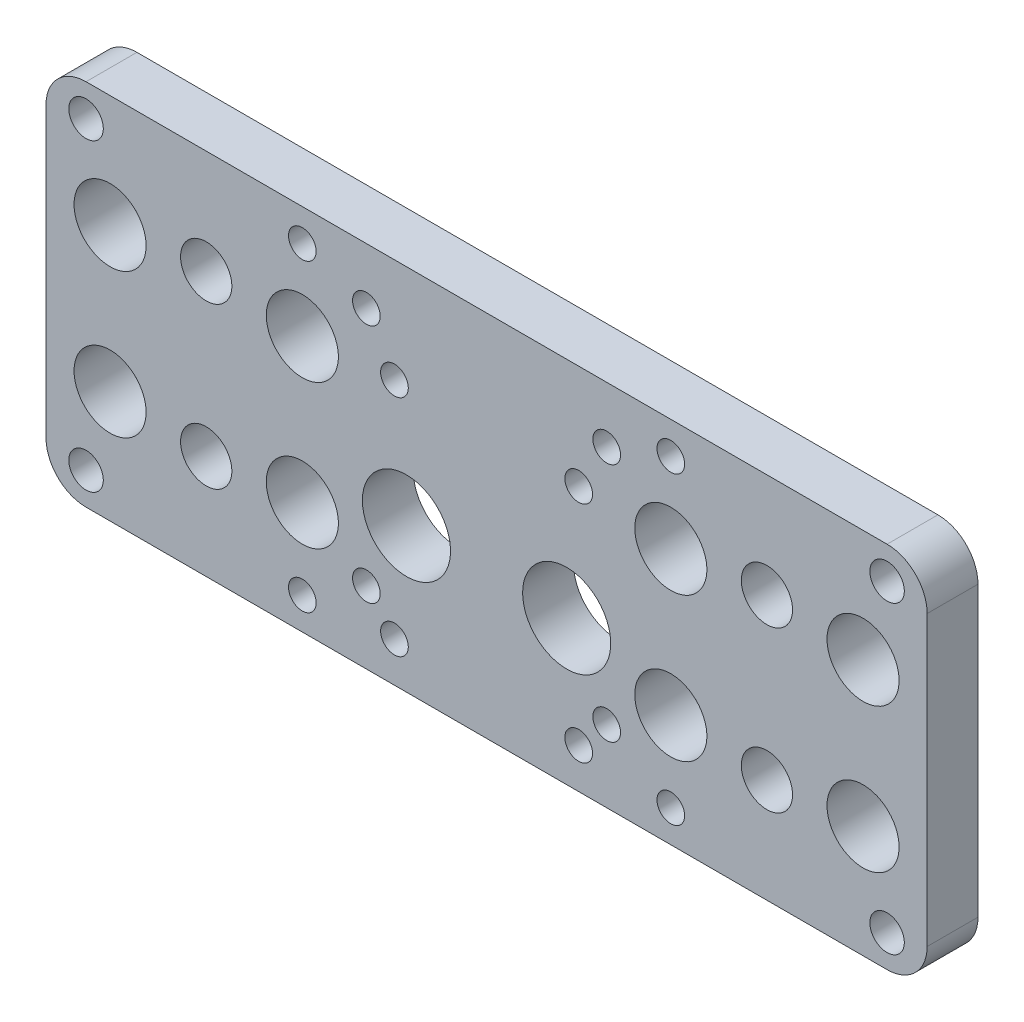
SolidWorks part; units mm, degrees
ref_plane "Front Plane" through (0, 0, 0) normal (0, 0, 1) x (1, 0, 0)
ref_plane "Top Plane" through (0, 0, 0) normal (0, 1, 0) x (1, 0, 0)
ref_plane "Right Plane" through (0, 0, 0) normal (1, 0, 0) x (0, 0, -1)
sketch "Sketch1" plane through (0, 0, 0) normal (0, 0, 1) x (1, 0, 0)
  line L0 (-55, -23) -> (-55, 23)
  line L1 (-55, -23) -> (55, -23)
  line L2 (-55, 23) -> (55, 23)
  line L3 (55, -23) -> (55, 23)
  line L4 (-55, -23) -> (55, 23) construction
  line L5 (-55, 23) -> (55, -23) construction
  point P1 (0, 0)
  dimension "D1" = 110
  dimension "D2" = 46
extrude "Boss-Extrude1" add sketch "Sketch1" along normal blind 6.35
sketch "Sketch2" plane through (0, 0, 0) normal (0, 0, -1) x (-1, 0, 0)
  line L0 (-35, -10) -> (-35, 10) construction
  line L1 (-35, -10) -> (35, -10) construction
  line L2 (-35, 10) -> (35, 10) construction
  line L3 (35, -10) -> (35, 10) construction
  line L4 (-35, -10) -> (35, 10) construction
  line L5 (-35, 10) -> (35, -10) construction
  point P1 (0, 0)
  dimension "D1" = 70
  dimension "D2" = 20
hole_wizard "M6 Clearance Hole1" positions "Sketch4" profile "Sketch3" hole size "M6" standard "ANSI Metric" end condition through all
sketch "Sketch4" plane through (0, 0, 0) normal (0, 0, -1) x (-1, 0, 0)
  point P0 (-35, 10)
  point P3 (-35, -10)
  point P6 (35, -10)
  point P9 (35, 10)
sketch "Sketch3" plane through (35, 10, 0) normal (1, 0, 0) x (0, 1, 0)
  line L0 (0, 0) -> (0, 6.35)
  line L1 (0, 6.35) -> (3.2, 6.35)
  line L2 (3.2, 6.35) -> (3.2, 0)
  line L5 (3.2, 0) -> (0, 0)
  line L11 (0, -6.35) -> (0, 107.95) construction
  dimension "Thru Hole Dia." = 6.4
  dimension "Thru Hole Depth" = 6.35
sketch "Sketch5" plane through (0, 0, 0) normal (0, 0, -1) x (-1, 0, 0)
  line L0 (-10, -5) -> (10, -5) construction
  circle A0 centre (-10, -5) radius 5.5
  circle A1 centre (10, -5) radius 5.5
  point P3 (0, 0)
  point P4 (0, -5)
  dimension "D3" = 11
  dimension "D1" = 20
  dimension "D4" = 5
extrude "Cut-Extrude1" cut sketch "Sketch5" against normal through all
sketch "Sketch7" plane through (0, 0, 0) normal (0, 0, -1) x (-1, 0, 0)
  line L1 (-23, -9) -> (23, -9) construction
  line L2 (-23, -9) -> (-23, 9) construction
  line L3 (-23, 9) -> (23, 9) construction
  line L4 (23, -9) -> (23, 9) construction
  line L5 (-23, -9) -> (23, 9) construction
  line L6 (-23, 9) -> (23, -9) construction
  line L7 (-47, -9) -> (-23, -9) construction
  line L8 (-47, -9) -> (-47, 9) construction
  line L9 (-47, 9) -> (-23, 9) construction
  line L10 (-23, -9) -> (-23, 9) construction
  line L11 (-47, -9) -> (-23, 9) construction
  line L12 (-47, 9) -> (-23, -9) construction
  line L13 (23, -9) -> (47, -9) construction
  line L14 (23, -9) -> (23, 9) construction
  line L15 (23, 9) -> (47, 9) construction
  line L16 (47, -9) -> (47, 9) construction
  line L17 (23, -9) -> (47, 9) construction
  line L18 (23, 9) -> (47, -9) construction
  circle A0 centre (-23, 9) radius 4.5
  circle A1 centre (-23, -9) radius 4.5
  circle A2 centre (23, -9) radius 4.5
  circle A3 centre (23, 9) radius 4.5
  circle A4 centre (-47, 9) radius 4.5
  circle A5 centre (-47, -9) radius 4.5
  circle A6 centre (47, 9) radius 4.5
  circle A7 centre (47, -9) radius 4.5
  point P0 (0, 0)
  point P10 (-35, 0)
  point P15 (35, 0)
  dimension "D3" = 9
  dimension "D1" = 46
  dimension "D2" = 18
  dimension "D4" = 24
  dimension "D5" = 24
extrude "Cut-Extrude2" cut sketch "Sketch7" against normal through all
sketch "Sketch8" plane through (0, 0, 0) normal (0, 0, -1) x (-1, 0, 0)
  line L1 (-23, -19) -> (23, -19) construction
  line L2 (-23, -19) -> (-23, 19) construction
  line L3 (-23, 19) -> (23, 19) construction
  line L4 (23, -19) -> (23, 19) construction
  line L5 (-23, -19) -> (23, 19) construction
  line L6 (-23, 19) -> (23, -19) construction
  line L7 (-50, -19) -> (50, -19) construction
  line L8 (-50, -19) -> (-50, 19) construction
  line L9 (-50, 19) -> (50, 19) construction
  line L10 (50, -19) -> (50, 19) construction
  line L11 (-50, -19) -> (50, 19) construction
  line L12 (-50, 19) -> (50, -19) construction
  point P0 (0, 0)
  point P6 (0, 0)
  dimension "D1" = 38
  dimension "D2" = 46
  dimension "D3" = 38
  dimension "D4" = 100
fillet "Fillet1" radius 5 4 edges at (-55, 23, 3.175) (-55, -23, 3.175) (55, -23, 3.175) (55, 23, 3.175)
hole_wizard "#8-32 Tapped Hole1" positions "Sketch10" profile "Sketch9" tap size "#8-32" standard "ANSI Inch" end condition through all
sketch "Sketch10" plane through (0, 0, 0) normal (0, 0, -1) x (-1, 0, 0)
  point P0 (-23, 19)
  point P3 (23, 19)
  point P6 (23, -19)
  point P9 (-23, -19)
sketch "Sketch9" plane through (23, 19, 0) normal (1, 0, 0) x (0, 1, 0)
  line L0 (0, 0) -> (0, 6.35)
  line L1 (0, 6.35) -> (1.7272, 6.35)
  line L2 (1.7272, 6.35) -> (1.7272, 0)
  line L5 (1.7272, 0) -> (0, 0)
  line L11 (0, -6.35) -> (0, 107.95) construction
  dimension "Thru Tap Drill Dia." = 3.4544
  dimension "Thru Tap Drill Depth" = 6.35
cosmetic thread "Hole Thread1" parameters "D2"=4.1656
cosmetic thread "Hole Thread2" parameters "D2"=4.1656
cosmetic thread "Hole Thread3" parameters "D2"=4.1656
cosmetic thread "Hole Thread4" parameters "D2"=4.1656
hole_wizard "#8 Clearance Hole1" positions "Sketch12" profile "Sketch11" hole size "#8" standard "ANSI Inch" end condition through all
sketch "Sketch12" plane through (0, 0, 0) normal (0, 0, -1) x (-1, 0, 0)
  point P0 (-50, 19)
  point P3 (-50, -19)
  point P6 (50, -19)
  point P9 (50, 19)
sketch "Sketch11" plane through (50, 19, 0) normal (1, 0, 0) x (0, 1, 0)
  line L0 (0, 0) -> (0, 6.35)
  line L1 (0, 6.35) -> (2.1526, 6.35)
  line L2 (2.1526, 6.35) -> (2.1526, 0)
  line L5 (2.1526, 0) -> (0, 0)
  line L11 (0, -6.35) -> (0, 107.95) construction
  dimension "Thru Hole Dia." = 4.3053
  dimension "Thru Hole Depth" = 6.35
sketch "Sketch13" plane through (0, 0, 0) normal (0, 0, -1) x (-1, 0, 0)
  line L1 (11.5, 10) -> (-11.5, 10) construction
  line L2 (11.5, 10) -> (11.5, -18) construction
  line L3 (11.5, -18) -> (-11.5, -18) construction
  line L4 (-11.5, 10) -> (-11.5, -18) construction
  line L5 (11.5, 10) -> (-11.5, -18) construction
  line L6 (11.5, -18) -> (-11.5, 10) construction
  line L7 (15, -14) -> (-15, -14) construction
  line L8 (15, -14) -> (15, 16) construction
  line L9 (15, 16) -> (-15, 16) construction
  line L10 (-15, -14) -> (-15, 16) construction
  line L11 (15, -14) -> (-15, 16) construction
  line L12 (15, 16) -> (-15, -14) construction
  point P0 (0, -4)
  point P5 (0, 0)
  point P7 (0, 1)
  dimension "D1" = 28
  dimension "D2" = 23
  dimension "D3" = 4
  dimension "D4" = 30
  dimension "D5" = 30
  dimension "D6" = 1
hole_wizard "#8-32 Tapped Hole2" positions "Sketch14" profile "Sketch15" tap size "#8-32" standard "ANSI Inch" end condition through all
sketch "Sketch14" plane through (0, 0, 0) normal (0, 0, -1) x (-1, 0, 0)
  point P0 (-11.5, 10)
  point P3 (11.5, 10)
  point P6 (11.5, -18)
  point P9 (-11.5, -18)
  point P12 (-15, -14)
  point P15 (15, -14)
  point P18 (15, 16)
  point P21 (-15, 16)
sketch "Sketch15" plane through (11.5, 10, 0) normal (1, 0, 0) x (0, 1, 0)
  line L0 (0, 0) -> (0, 6.35)
  line L1 (0, 6.35) -> (1.7272, 6.35)
  line L2 (1.7272, 6.35) -> (1.7272, 0)
  line L5 (1.7272, 0) -> (0, 0)
  line L11 (0, -6.35) -> (0, 107.95) construction
  dimension "Thread Major Dia." = 3.4544
  dimension "Thru Tap Drill Depth" = 6.35
